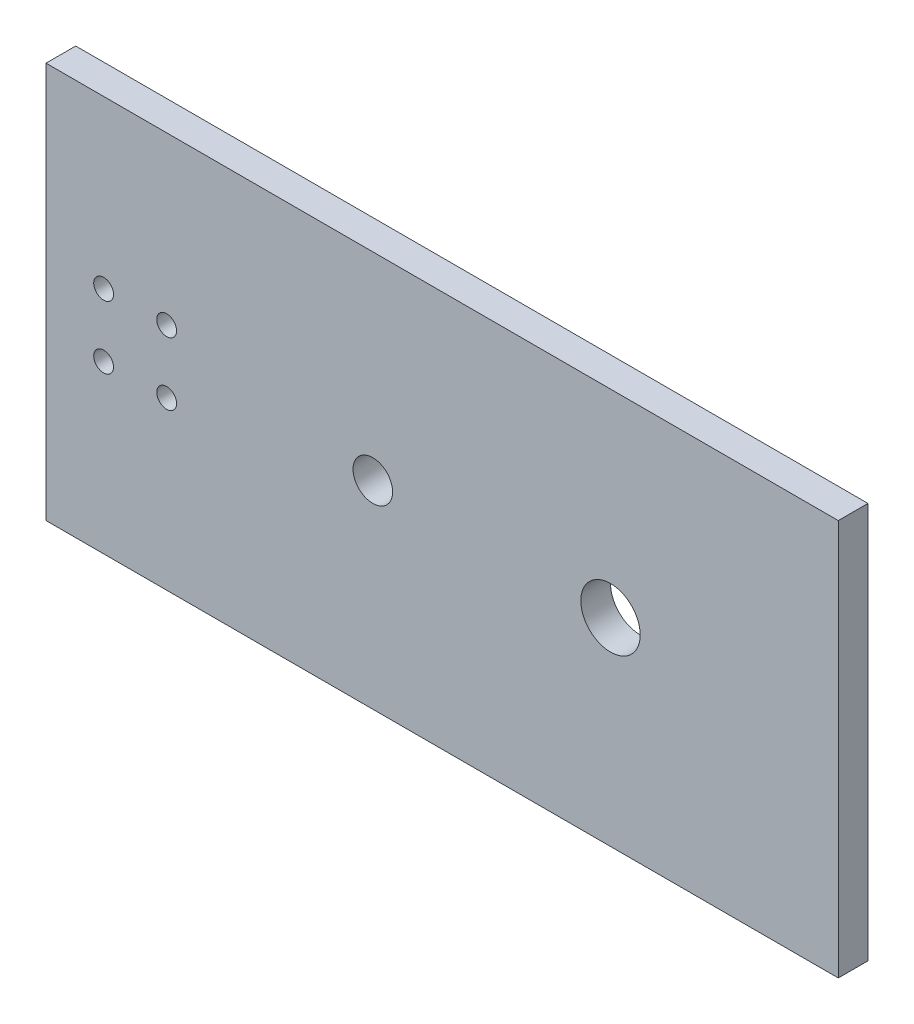
SolidWorks part; units mm, degrees
ref_plane "Front Plane" through (0, 0, 0) normal (0, 0, 1) x (1, 0, 0)
ref_plane "Top Plane" through (0, 0, 0) normal (0, 1, 0) x (1, 0, 0)
ref_plane "Right Plane" through (0, 0, 0) normal (1, 0, 0) x (0, 0, -1)
sketch "Sketch1" plane through (0, 0, 0) normal (0, 0, 1) x (1, 0, 0)
  line L1 (0, 0) -> (80, 0)
  line L2 (0, 0) -> (0, 40)
  line L3 (0, 40) -> (80, 40)
  line L4 (80, 0) -> (80, 40)
  dimension "D1" = 80
  dimension "D2" = 40
extrude "Boss-Extrude1" add sketch "Sketch1" along normal blind 3 contours L3 L4 L1 L2
sketch "Sketch2" plane through (0, 0, 3) normal (0, 0, 1) x (1, 0, 0)
  line L0 (0, 20) -> (80, 20) construction
  line L1 (0, 0) -> (0, 40) construction
  line L2 (80, 0) -> (80, 40) construction
  line L3 (9, 20) -> (13.5, 20) construction
  line L4 (4.318, 15.318) -> (13.682, 15.318) construction
  line L5 (4.318, 15.318) -> (4.318, 24.682) construction
  line L6 (4.318, 24.682) -> (13.682, 24.682) construction
  line L7 (13.682, 15.318) -> (13.682, 24.682) construction
  line L8 (4.318, 15.318) -> (13.682, 24.682) construction
  line L9 (4.318, 24.682) -> (13.682, 15.318) construction
  circle A1 centre (33, 20) radius 2
  circle A2 centre (57, 20) radius 3
  circle A3 centre (12.182, 23.182) radius 1
  circle A4 centre (9, 20) radius 4.5 construction
  circle A5 centre (12.182, 16.818) radius 1
  circle A6 centre (5.818, 16.818) radius 1
  circle A7 centre (5.818, 23.182) radius 1
  point P6 (9, 20)
  point P27 (9, 20)
  point P28 (12.182, 16.818)
  point P29 (5.818, 23.182)
  point P30 (0, 0)
  dimension "D1" = 9
  dimension "D2" = 4
  dimension "D3" = 6
  dimension "D5" = 2
  dimension "D7" = 9
  dimension "D4" = 24
  dimension "D6" = 24
  dimension "D8" = 1.5
extrude "Cut-Extrude1" cut sketch "Sketch2" against normal through all contours A1 L0 | L0 A1 | A2 L0 | L0 A2 | A7 | A3 | A5 | A6
